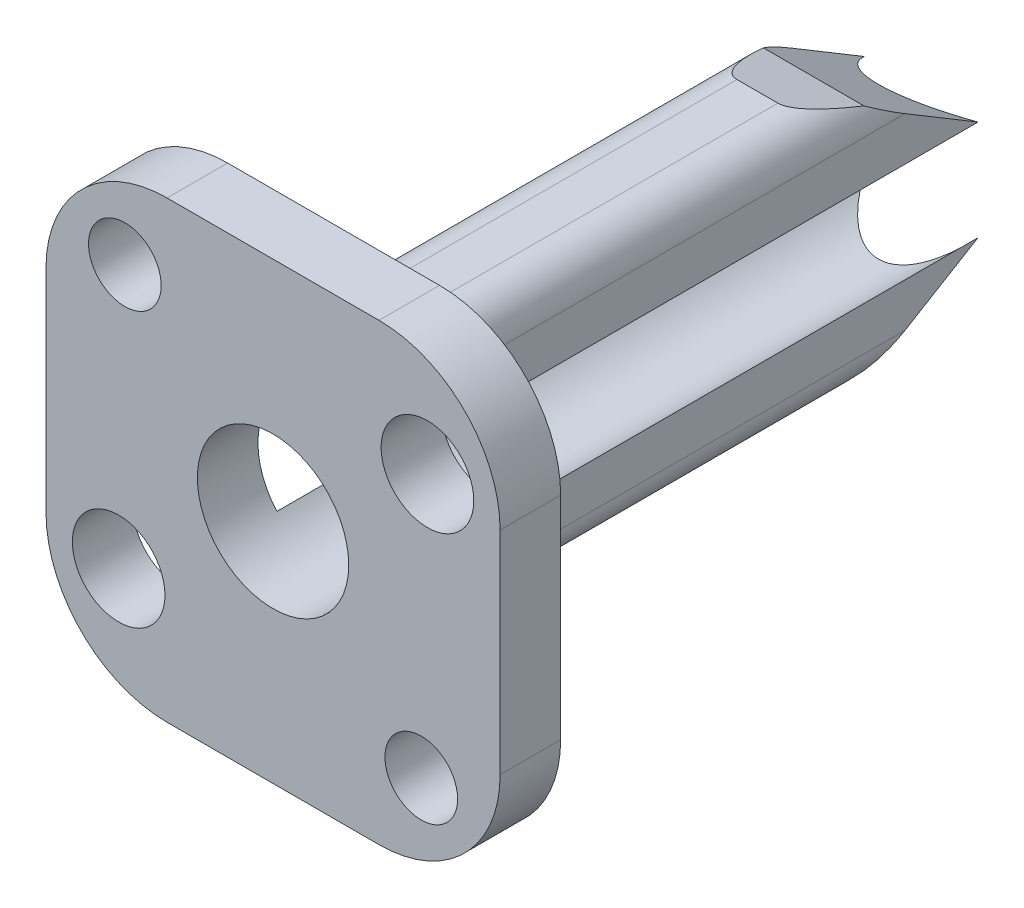
SolidWorks part; units mm, degrees
note: The reader was unsure of these and kept them because the rebuilt part matched: shared geometry of "Croquis2<3>", "Croquis2<4>".
ref_plane "Alzado" through (0, 0, 0) normal (1, 0, 0) x (0, 1, 0)
ref_plane "Planta" through (0, 0, 0) normal (0, 0, 1) x (0, 1, 0)
ref_plane "Vista lateral" through (0, 0, 0) normal (0, 1, 0) x (-1, 0, 0)
sketch "Croquis2" plane through (0, 0, 0) normal (0, 0, 1) x (0, 1, 0)
  line L0 (-21.5, -9.375) -> (21.5, -9.375)
  line L1 (-37.5, -37.5) -> (37.5, -37.5)
  line L2 (-37.5, -37.5) -> (-37.5, 37.5)
  line L3 (-37.5, 37.5) -> (37.5, 37.5)
  line L4 (37.5, -37.5) -> (37.5, 37.5)
  line L5 (-37.5, -37.5) -> (37.5, 37.5) construction
  line L6 (-37.5, 37.5) -> (37.5, -37.5) construction
  line L11 (-21.5, -9.375) -> (-21.5, 9.375)
  line L12 (21.5, -9.375) -> (21.5, 9.375)
  line L13 (-21.5, 9.375) -> (21.5, 9.375)
  line L14 (-21.5, -9.375) -> (21.5, 9.375) construction
  line L15 (21.5, -9.375) -> (-21.5, 9.375) construction
  line L16 (37.5, 0) -> (0, 0) construction
  circle A0 centre (0, 0) radius 12.5
  point P0 (0, 0)
  point P7 (0, 0)
  dimension "D4" = 25
  dimension "D1" = 75
  dimension "D2" = 75
  dimension "D3" = 43
  dimension "D6" = 18.75
extrude "Saliente-Extruir1" add sketch "Croquis2" along normal blind 10 contours A0 L13 L4 L3 L2 L1 L0 L11 | A0 L13 L11 L0 | L0 A0 L13 | L13 A0 | L0 A0 | A0 L0 L4 L13
extrude "Saliente-Extruir2" add sketch "Croquis2<3>" against normal blind 100 contours A0 L13 L11 L0 | A0 L0 L4 L13
sketch "Croquis2<3>" plane through (0, 0, 0) normal (0, 0, 1) x (0, 1, 0) same geometry as "Croquis2"
chamfer "Chaflán1" distance 15 distance2 25 1 edges at (0, 21.5, -100)
chamfer "Chaflán2" distance 25 distance2 15 1 edges at (0, -21.5, -100)
extrude "Cortar-Extruir1" cut sketch "Croquis2<4>" along normal up to next contours L0 A0 L13 | L0 A0 | L13 A0
sketch "Croquis2<4>" plane through (0, 0, 0) normal (0, 0, 1) x (0, 1, 0) same geometry as "Croquis2"
chamfer "Chaflán3" distance 5 2 edges at (0, -21.5, -75) (0, 21.5, -75)
fillet "Redondeo1" radius 6 4 edges at (-9.375, -21.5, -35) (9.375, -21.5, -35) (9.375, 21.5, -35) (-9.375, 21.5, -35)
fillet "Redondeo2" radius 20 4 edges at (-37.5, -37.5, 5) (37.5, -37.5, 5) (-37.5, 37.5, 5) (37.5, 37.5, 5)
sketch "Sketch1" plane through (0, 0, 10) normal (0, 0, 1) x (1, 0, 0)
  line L0 (37.5, -17.5) -> (37.5, 17.5) construction
  line L1 (-37.5, -17.5) -> (-37.5, 17.5) construction
  line L2 (17.5, -37.5) -> (-17.5, -37.5) construction
  line L4 (17.5, 37.5) -> (-17.5, 37.5) construction
  circle A0 centre (25.5, 19.5) radius 7.65
  circle A1 centre (-24.48, 24.48) radius 6
  circle A2 centre (-25.5, -19.5) radius 7.65
  circle A3 centre (24.48, -24.48) radius 6
  dimension "D1" = 15.3
  dimension "D2" = 15.3
  dimension "D7" = 12
  dimension "D12" = 12
  dimension "D3" = 12
  dimension "D4" = 18
  dimension "D5" = 12
  dimension "D6" = 18
  dimension "D8" = 13.02
  dimension "D9" = 13.02
  dimension "D10" = 13.02
  dimension "D11" = 13.02
extrude "Cut-Extrude2" cut sketch "Sketch1" against normal blind 10
